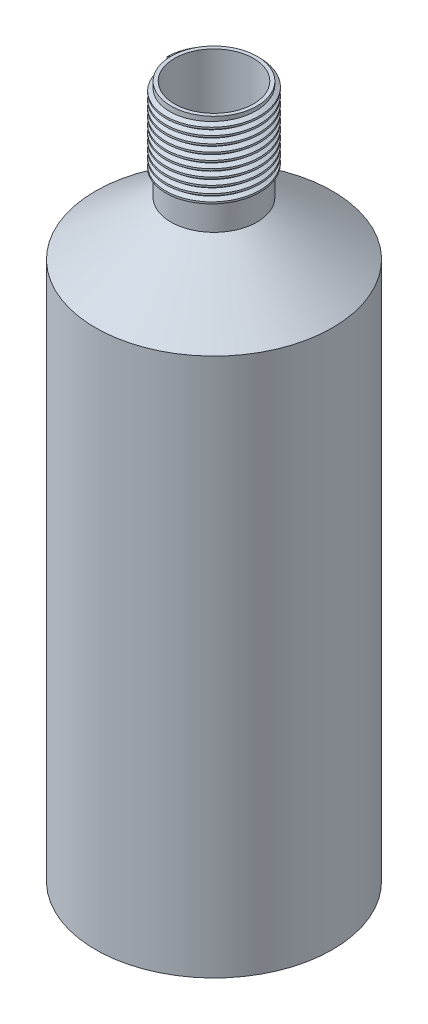
SolidWorks part; units mm, degrees
material "玻璃"
ref_plane "前视基准面" through (0, 0, 0) normal (0, 0, 1) x (1, 0, 0)
ref_plane "上视基准面" through (0, 0, 0) normal (0, 1, 0) x (1, 0, 0)
ref_plane "右视基准面" through (0, 0, 0) normal (1, 0, 0) x (0, 0, -1)
sketch "草图1" plane through (0, 0, 0) normal (0, 0, 1) x (1, 0, 0)
  line L0 (0, 0) -> (33, 0)
  line L1 (33, 0) -> (33, 150)
  line L2 (33, 150) -> (12, 165)
  line L3 (12, 165) -> (12, 193)
  line L4 (12, 193) -> (11, 193)
  line L5 (11, 193) -> (11, 165)
  line L6 (11, 165) -> (32, 150)
  line L7 (32, 150) -> (32, 1)
  line L8 (32, 1) -> (0, 1)
  line L9 (0, 1) -> (0, 0)
  dimension "D1" = 33
  dimension "D2" = 150
  dimension "D3" = 15
  dimension "D4" = 12
  dimension "D5" = 28
  dimension "D6" = 1
  dimension "D7" = 1
revolve "旋转1" add sketch "草图1" angle 360 about L9
thread "螺纹线1" pitch 2 method extrude profile "螺纹线轮廓1" start angle 0, offset 0, length 20, pitch 2, diameter 24
ref_plane "基准面1" through (-12, 193, 0) normal (0, 0, 1) x (-1, 0, 0)
sketch "螺纹线轮廓1" plane through (-12, 193, 0) normal (0, 0, 1) x (-1, 0, 0)
  line L0 (0, 0) -> (0, 2) construction
  line L11 (0, 1.75) -> (0, 0)
  line L12 (0, 0) -> (1.0825, 0.625)
  line L13 (1.0825, 0.625) -> (1.0825, 1.125)
  line L15 (1.0825, 1.125) -> (0, 1.75)
  line L17 (1.0825, 0.875) -> (0, 0.875) construction
  point P3 (0, 0)
  dimension "Pitch" = 2
  dimension "Profile_Angle" = 60
  dimension "Profile_Land" = 0.5
  dimension "Profile_Height" = 1.0825
